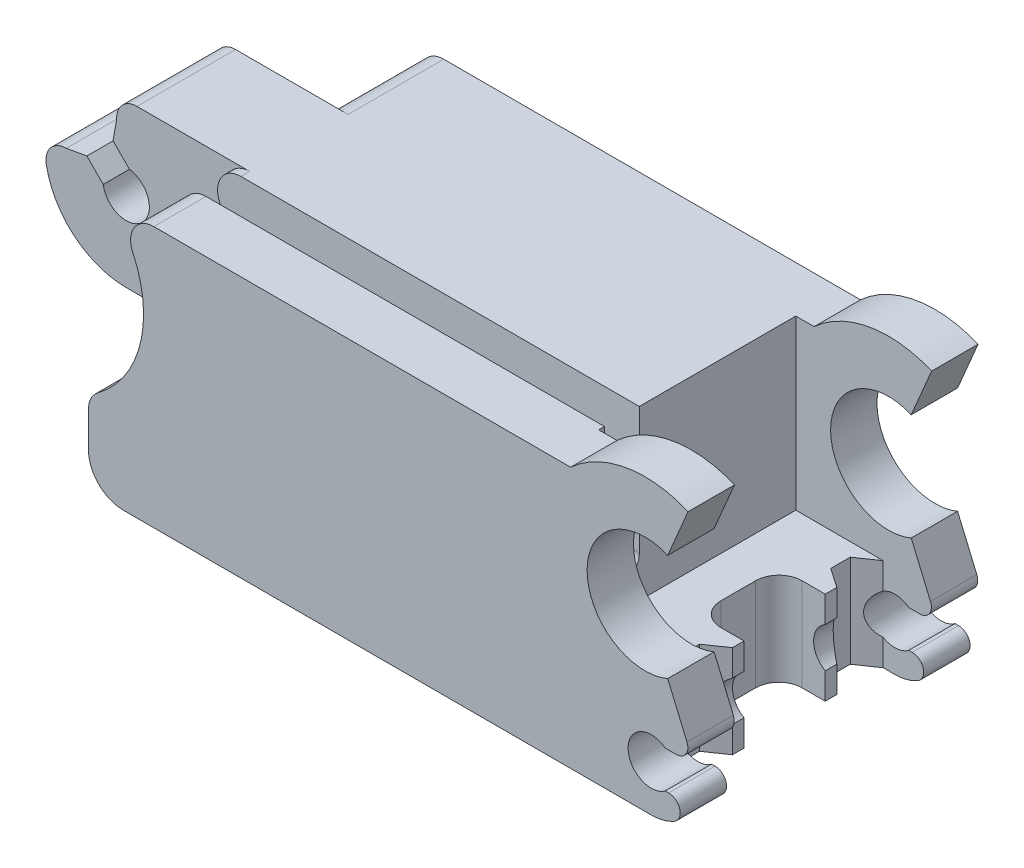
SolidWorks part; units mm, degrees
ref_plane "Front Plane" through (0, 0, 0) normal (0, 0, 1) x (1, 0, 0)
ref_plane "Top Plane" through (0, 0, 0) normal (0, 1, 0) x (1, 0, 0)
ref_plane "Right Plane" through (0, 0, 0) normal (1, 0, 0) x (0, 0, -1)
sketch "Sketch1" plane through (0, 0, 0) normal (0, 0, 1) x (1, 0, 0)
  line L0 (0, 0) -> (9.5, 0) construction
  line L1 (-62.5, 9.5) -> (9.5, 9.5)
  line L2 (-62.5, 9.5) -> (-62.5, -15.5)
  line L3 (-62.5, -15.5) -> (9.5, -15.5)
  line L4 (9.5, 9.5) -> (9.5, -15.5)
  line L5 (0, 0) -> (3.7119, 8.7448) construction
  line L6 (3.7119, 8.7448) -> (1.856, 4.3724)
  line L7 (3.7119, -8.7448) -> (1.856, -4.3724)
  line L8 (1.736, -9.9) -> (1.736, -13.1)
  line L9 (1.736, -9.9) -> (4.2021, -9.9)
  line L10 (1.736, -13.1) -> (4.2021, -13.1)
  line L11 (-52.7172, 1.9799) -> (-54.9799, -0.2828)
  line L12 (-62.5, -15.5) -> (-43, -15.5)
  line L13 (-62.5, -15.5) -> (-62.5, -6.5)
  line L16 (-52.7172, 1.9799) -> (-54.1314, 3.3941)
  line L17 (-58.1668, 0.8188) -> (-59.6208, 2.2728)
  line L18 (-53, 0) -> (-53.8485, 0.8485) construction
  line L19 (-56.3941, 1.1314) -> (-58.1668, 0.8188)
  line L20 (-53, 7) -> (-6.4226, 7)
  line L21 (-54.9799, -0.2828) -> (-56.3941, 1.1314)
  line L22 (-54.1314, 3.3941) -> (-53.8188, 5.1668)
  line L23 (-53.8188, 5.1668) -> (-55.2728, 6.6208)
  line L24 (-53, -7) -> (-43, -7)
  line L25 (-43, -7) -> (-43, -15.5)
  line L26 (4.2021, -9.9) -> (3.7119, -8.7448)
  line L27 (-43, -7) -> (-43, 0) construction
  line L28 (-48, -7) -> (-48, -15.5)
  line L29 (-53, 0) -> (-55, 0) construction
  circle A0 centre (0, 0) radius 2 construction
  circle A1 centre (-53, 0) radius 2
  circle A2 centre (0, 0) radius 5
  circle A3 centre (0, 0) radius 9.5
  circle A4 centre (0.536, -11.5) radius 2
  circle A5 centre (0.536, -11.5) radius 4
  circle A6 centre (-53, 0) radius 7
  circle A8 centre (-53, 0) radius 6 construction
  circle A9 centre (-53, 0) radius 6.5 construction
  point P39 (4.536, -11.5)
  dimension "D1" = 4
  dimension "D2" = 4
  dimension "D4" = 10
  dimension "D9" = 4
  dimension "D13" = 8
  dimension "D20" = 12
  dimension "D23" = 19
  dimension "D3" = 53
  dimension "D5" = 25
  dimension "D6" = 9.5
  dimension "D8" = 67
  dimension "D10" = 2
  dimension "D12" = 3.2
  dimension "D16" = 3.2
  dimension "D14" = 2
  dimension "D15" = 4.536
  dimension "D24" = 10
  dimension "D21" = 5
  dimension "D18" = 125
  dimension "D19" = 1.8
  dimension "D25" = 45
  dimension "D7" = 4.5
  dimension "D11" = 2
  dimension "D17" = 5
  dimension "D22" = 0.5
extrude "Boss-Extrude1" add sketch "Sketch1" along normal mid plane 25 contours A6 L23 L22 L16 A1 L21 L19 L17 | A6 L24 L25 L3 A5 A3 L20 | A5 A3 L7 A2 L6 | A3 A5 | L9 A5 A3 L10 A4 | A5 L26 A3 region at (1.8485, 9.0856, 0) region at (-26.1779, -4.322, 0) region at (-48.1903, 4.8097, 0) region at (0.3999, -8.5786, 0) region at (0.4428, -9.4998, 0) region at (3.7778, -9.0652, 0)
fillet "Fillet1" radius 1 2 edges at (4.2021, -13.1, 0) (4.2021, -9.9, 0)
sketch "Sketch3" plane through (0, 0, 0) normal (0, 0, 1) x (1, 0, 0)
  line L0 (-43, -15.5) -> (0.536, -15.5) construction
  line L1 (-8, 10.2107) -> (7.5521, 10.2107)
  line L2 (-8, 10.2107) -> (-8, -15.5)
  line L3 (-8, -15.5) -> (7.5521, -15.5)
  line L4 (7.5521, 10.2107) -> (7.5521, -15.5)
  dimension "D1" = 8
extrude "Cut-Extrude1" cut sketch "Sketch3" against normal offset from surface 4 and the other way offset from surface 4 contours L4 L1 L2 L3 region at (-0.2239, -2.6446, 0) up to face at (-27.411, -3.1826, -12.5) other way up to face at (-27.411, -3.1826, 12.5)
sketch "Sketch5" plane through (0, 0, 12.5) normal (0, 0, 1) x (1, 0, 0)
  line L0 (-53, 7) -> (-6.4226, 7) construction
  line L1 (-43, -7) -> (-73.6432, -7)
  line L2 (-43, -7) -> (-43, 7)
  line L3 (-43, 7) -> (-73.6432, 7)
  line L4 (-73.6432, -7) -> (-73.6432, 7)
extrude "Cut-Extrude2" cut sketch "Sketch5" against normal offset from surface (8.25 mm away) 4.25 up to face at (-0.7087, -5.8791, 8.5) offset beyond the face yes
sketch "Sketch6" plane through (0, 0, -12.5) normal (0, 0, -1) x (-1, 0, 0)
  line L8 (43, -7) -> (73.6432, -7)
  line L9 (73.6432, -7) -> (73.6432, 7)
  line L10 (73.6432, 7) -> (43, 7)
  line L11 (43, 7) -> (43, -7)
  line L12 (43, -7) -> (73.6432, -7)
  line L13 (73.6432, -7) -> (73.6432, 7)
  line L14 (73.6432, 7) -> (43, 7)
  line L15 (43, 7) -> (43, -7)
  line M10 (43, -7) -> (53, -7)
  arc M11 (53, -7) -> (59.6208, 2.2728) centre (53, 0) ccw
  line M12 (59.6208, 2.2728) -> (58.1668, 0.8188)
  line M13 (58.1668, 0.8188) -> (56.3941, 1.1314)
  line M14 (56.3941, 1.1314) -> (54.9799, -0.2828)
  arc M15 (54.9799, -0.2828) -> (52.7172, 1.9799) centre (53, 0) cw
  line M16 (52.7172, 1.9799) -> (54.1314, 3.3941)
  line M17 (54.1314, 3.3941) -> (53.8188, 5.1668)
  line M18 (53.8188, 5.1668) -> (55.2728, 6.6208)
  arc M19 (55.2728, 6.6208) -> (53, 7) centre (53, 0) ccw
  line M20 (53, 7) -> (6.4226, 7)
  dimension "D1" = 0
extrude "Cut-Extrude3" cut sketch "Sketch6" against normal offset from surface (8.25 mm away) 4.25 contours M10 M11 M12 M13 M14 M15 M16 M17 M18 M19 M20 region at (-49.9173, -0.455, -12.5) up to face at (-0.7087, -5.8791, -8.5) offset beyond the face yes
sketch "Sketch7" plane through (0, 0, 0) normal (0, 0, 1) x (1, 0, 0)
  line L9 (-55.2728, 6.6208) -> (-53.8188, 5.1668)
  line L10 (-55.2728, 6.6208) -> (-53.8188, 5.1668)
  line L11 (-53.8188, 5.1668) -> (-54.1314, 3.3941)
  line L12 (-53.8188, 5.1668) -> (-54.1314, 3.3941)
  line L13 (-54.1314, 3.3941) -> (-52.7172, 1.9799)
  line L14 (-54.1314, 3.3941) -> (-52.7172, 1.9799)
  line L15 (-43, 7) -> (-53, 7)
  line L16 (-43, -7) -> (-43, 7)
  line L17 (-54.9799, -0.2828) -> (-56.3941, 1.1314)
  line L25 (-43, -7) -> (-43, 7)
  line L27 (-54.9799, -0.2828) -> (-56.3941, 1.1314)
  line L28 (-56.3941, 1.1314) -> (-58.1668, 0.8188)
  line L29 (-56.3941, 1.1314) -> (-58.1668, 0.8188)
  line L30 (-58.1668, 0.8188) -> (-59.6208, 2.2728)
  line L31 (-58.1668, 0.8188) -> (-59.6208, 2.2728)
  line L32 (-43, 7) -> (-53, 7)
  line L34 (-53, -7) -> (-43, -7)
  line L37 (-53, -7) -> (-43, -7)
  arc A1 (-53, 7) -> (-55.2728, 6.6208) centre (-53, 0) ccw
  arc A5 (-53, 7) -> (-55.2728, 6.6208) centre (-53, 0) ccw
  arc A9 (-54.9799, -0.2828) -> (-52.7172, 1.9799) centre (-53, 0) ccw
  arc A10 (-54.9799, -0.2828) -> (-52.7172, 1.9799) centre (-53, 0) ccw
  arc A11 (-59.6208, 2.2728) -> (-53, -7) centre (-53, 0) ccw
  arc A12 (-59.6208, 2.2728) -> (-53, -7) centre (-53, 0) ccw
  dimension "D1" = 0
fillet "Fillet2" radius 1.75 2 edges at (-59.6208, 2.2728, 0) (-55.2728, 6.6208, 0)
sketch "Sketch8" [suppressed] plane through (0, 0, -4.25) normal (0, 0, 1) x (1, 0, 0)
  line L0 (-53, 7) -> (-43, 7)
  line L1 (-43, 7) -> (-43, -7)
  line L2 (-43, -7) -> (-53, -7)
  arc A0 (-54.9799, -0.2828) -> (-52.7172, 1.9799) centre (-53, 0) ccw construction
  arc A1 (-54.9799, -0.2828) -> (-52.7172, 1.9799) centre (-53, 0) ccw
  circle A2 centre (-53, 0) radius 6 construction
  circle A3 centre (-53, 0) radius 7
  dimension "D1" = 12
sketch "Sketch10" plane through (0, 0, 4.25) normal (0, 0, 1) x (1, 0, 0)
  line L1 (-48, -7) -> (-48, -15.5) construction
  line L2 (-48, -7) -> (-48, -15.5)
  line L3 (-43, 7) -> (-46.2131, 7)
  line L6 (-52.0708, 7) -> (-43, 7) construction
  line L7 (-43, 7) -> (-43, -15.5)
  line L8 (-43, -15.5) -> (-48, -15.5)
  arc A0 (3.7119, 8.7448) -> (-6.4226, 7) centre (0, 0) ccw construction
  arc A1 (-54.9799, -0.2828) -> (-52.7172, 1.9799) centre (-53, 0) ccw construction
  arc A2 (3.7119, 8.7448) -> (-6.4226, 7) centre (0, 0) ccw construction
  arc A3 (-54.9799, -0.2828) -> (-52.7172, 1.9799) centre (-53, 0) ccw construction
  circle A4 centre (-53, 0) radius 9.75
  line M9 (-53, -7) -> (-43, -7)
  line M10 (-43, -7) -> (-43, 7)
  line M11 (-43, 7) -> (-52.0708, 7)
  dimension "D1" = 9.5
  dimension "D2" = 19.5
extrude "Boss-Extrude3" add sketch "Sketch10" along normal up to surface (8.25 mm away) contours A4 M9 M10 M11 | A4 L2 L8 L7 M9 region at (-45.4396, -11.3712, 4.25) region at (-43.889, -3.8566, 4.25) up to face at (-6.0933, -5.8791, 12.5)
sketch "Sketch41" plane through (0, 0, -4.25) normal (0, 0, -1) x (-1, 0, 0)
  line L0 (43, 7) -> (46.2131, 7) construction
  line L1 (43, 7) -> (43, -15.5) construction
  line L2 (43, -15.5) -> (48, -15.5) construction
  line L3 (48, -7) -> (48, -15.5) construction
  line L4 (43, 7) -> (46.2131, 7)
  line L5 (43, 7) -> (43, -15.5)
  line L6 (43, -15.5) -> (48, -15.5)
  line L7 (48, -7) -> (48, -15.5)
  circle A1 centre (53, 0) radius 9.75
  circle A2 centre (53, 0) radius 9.75
  line M10 (52.0708, 7) -> (43, 7)
  line M11 (43, 7) -> (43, -7)
  line M12 (43, -7) -> (53, -7)
  dimension "D1" = 0
extrude "Boss-Extrude6" add sketch "Sketch41" along normal up to surface (8.25 mm away) contours A2 L5 L6 L7 M12 | A2 M10 M11 M12 region at (-44.6065, 6.8564, -4.25) region at (-45.4396, -11.3712, -4.25) up to face at (-6.0933, -5.8791, -12.5)
fillet "Fillet4" radius 2 4 edges at (-48, -8.3703, 8.375) (-46.2131, 7, 8.375) (-48, -8.3703, -8.375) (-46.2131, 7, -8.375)
ref_plane "Plane1" through (0, 0, 6.5) normal (0, 0, 1) x (1, 0, 0)
sketch "Sketch11" plane through (0, 0, 6.5) normal (0, 0, -1) x (-1, 0, 0)
  line L0 (51.8208, 5.4642) -> (1.1792, -5.4642)
  arc A0 (52.7172, 1.9799) -> (54.9799, -0.2828) centre (53, 0) ccw construction
  arc A1 (52.7172, 1.9799) -> (54.9799, -0.2828) centre (53, 0) ccw construction
  arc A2 (-1.9537, -4.6025) -> (-1.9537, 4.6025) centre (0, 0) ccw construction
  arc A3 (-1.9537, -4.6025) -> (-1.9537, 4.6025) centre (0, 0) ccw construction
  circle A4 centre (53, 0) radius 5 construction
  circle A5 centre (0, 0) radius 5 construction
  circle A6 centre (53, 0) radius 5.59 construction
  circle A7 centre (0, 0) radius 5.59 construction
  dimension "D3" = 0.59
sweep "Cut-Sweep1" cut path "Sketch11" circular profile diameter 3 parameters "D3"=3
fillet "Fillet6" radius 3 2 edges at (-48, -15.5, 8.375) (-48, -15.5, -8.375)
sketch "Sketch24" plane through (0, 0, 0) normal (0, 0, 1) x (1, 0, 0)
  line L0 (-45, -15.5) -> (0.536, -15.5) construction
  line L1 (-45, -15.5) -> (0.536, -15.5) construction
  line L6 (-24.5, -13.5) -> (-24.5, -15.5) construction
  line L7 (-11.5, -13.5) -> (-11.5, -15.5) construction
  line L8 (-41.5, -13.5) -> (-41.5, -15.5)
  line L9 (-28.5, -13.5) -> (-28.5, -15.5)
  line L10 (-41.5, -15.5) -> (-28.5, -15.5)
  line L11 (-24.5, -15.5) -> (-11.5, -15.5) construction
  line L12 (-35, -7) -> (-48, -7)
  line L13 (-48, -9.4373) -> (-48, -12.5) construction
  line L14 (-48, -7) -> (-48, -15.5)
  line L15 (-48, -15.5) -> (-28.5, -15.5)
  circle A0 centre (-18, -13.5) radius 2 construction
  arc A5 (-54.9799, -0.2828) -> (-52.7172, 1.9799) centre (-53, 0) ccw construction
  arc A6 (-54.9799, -0.2828) -> (-52.7172, 1.9799) centre (-53, 0) ccw construction
  circle A7 centre (-35, -13.5) radius 2 construction
  arc A8 (-11.5, -13.5) -> (-24.5, -13.5) centre (-18, -13.5) ccw construction
  arc A9 (-28.5, -13.5) -> (-41.5, -13.5) centre (-35, -13.5) ccw
  circle A10 centre (-18, -13.5) radius 2.2 construction
  circle A11 centre (-35, -13.5) radius 2.2
  dimension "D1" = 4
  dimension "D2" = 18
  dimension "D3" = 4.5
  dimension "D4" = 18
  dimension "D5" = 0.2
extrude "Cut-Extrude6" cut sketch "Sketch24" against normal mid plane 8.5 contours A10 L11 L7 A8 L6 | A11 L10 L9 A9 L8 | A9 L12 L14 L15 L8 region at (-39.4864, -9.0136, 0) region at (-44.0872, -10.8555, 0)
sketch "Sketch45" plane through (0, 0, 0) normal (0, 0, 1) x (1, 0, 0)
  line L0 (3.612, -8.5093) -> (1.9537, -4.6025) construction
  line L1 (3.612, -8.5093) -> (1.9537, -4.6025)
  arc A0 (1.736, -9.9) -> (1.736, -13.1) centre (0.536, -11.5) ccw construction
  arc A1 (1.736, -9.9) -> (1.736, -13.1) centre (0.536, -11.5) ccw
sketch "Sketch47" plane through (0, 7, 0) normal (0, 1, 0) x (1, 0, 0)
  line L0 (-8, -5) -> (-44.0122, -5) construction
  line L1 (-5.5113, -5) -> (-48.8713, -5)
  line L2 (-44.0122, -8) -> (-8, -8) construction
  line L3 (-48.8713, -8) -> (-5.5113, -8)
  line L4 (-48.8713, -8) -> (-48.8713, -5)
  line L5 (-5.5113, -5) -> (-5.5113, -8)
extrude "Cut-Extrude7" cut sketch "Sketch47" against normal up to surface (11.5293 mm away) up to face at (-43.9108, 3.7419, 6.6784)
sketch "Sketch50" plane through (0, 0, 8.5) normal (0, 0, -1) x (-1, 0, 0)
  line L0 (0.464, -13.2321) -> (0.464, -15.5)
  line L1 (8, -15.5) -> (-0.536, -15.5) construction
  line L2 (8, 7) -> (8, -15.5) construction
  line L3 (8, 7) -> (8, -15.5)
  line L4 (0.464, -15.5) -> (8, -15.5)
  line L5 (0.464, -9.7679) -> (0.464, -7.5)
  line L6 (0.464, -7.5) -> (8, -7.5)
  arc A0 (-1.736, -13.1) -> (-1.736, -9.9) centre (-0.536, -11.5) ccw construction
  arc A1 (-1.736, -13.1) -> (-1.736, -9.9) centre (-0.536, -11.5) ccw
  arc M11 (-1.736, -9.9) -> (-1.736, -13.1) centre (-0.536, -11.5) cw
  line M15 (-0.536, -15.5) -> (8, -15.5)
  line M16 (8, -15.5) -> (8, 7)
  dimension "D1" = 4
  dimension "D2" = 4
extrude "Boss-Extrude7" add sketch "Sketch50" along normal up to vertex contours L6 L5 L0 M11 M15 M16 region at (-4.3746, -11.5, 8.5) up to point (0.536, -15.5, -8.5)
sketch "Sketch51" plane through (0, -15.5, 0) normal (0, -1, 0) x (1, 0, 0)
  line L0 (-0.464, -8.5) -> (-0.464, 8.5) construction
  line L1 (-0.464, -8.5) -> (-0.464, 8.5)
  line L2 (-2.144, 5.66) -> (-2.144, 7.34)
  line L3 (-2.144, 7.34) -> (-0.464, 8.5)
  line L4 (-2.144, 6.5) -> (-0.464, 6.5) construction
  line L5 (-2.144, 5.66) -> (-0.464, 4.5)
  line L6 (-0.464, 0) -> (-3.9441, 0) construction
  line L7 (-2.144, -5.66) -> (-0.464, -4.5)
  line L8 (-2.144, -5.66) -> (-2.144, -7.34)
  line L9 (-2.144, -7.34) -> (-0.464, -8.5)
  line L12 (-0.464, 3.5) -> (-0.464, -4)
  line L13 (-0.464, 3.5) -> (-4.464, 3.5)
  line L14 (-0.464, 3.5) -> (-0.464, -3.5)
  line L15 (-0.464, -3.5) -> (-4.464, -3.5)
  line L16 (-4.464, 3.5) -> (-4.464, -3.5)
  point P2 (-2.144, 6.5)
  point P6 (-2.144, 6.5)
  point P17 (-4.464, 0)
  point P20 (0, 0)
  point P21 (0, 0)
  point P23 (-4.464, -3.4312)
  point P24 (0, 0)
  point P25 (0, 0)
  point P26 (-8, -3.3962)
  point P27 (0, 0)
  line M26 (-0.464, -8.5) -> (-0.464, 8.5)
  dimension "D1" = 2
  dimension "D2" = 1.68
  dimension "D3" = 1.68
  dimension "D4" = 7
  dimension "D5" = 4
extrude "Cut-Extrude8" cut sketch "Sketch51" against normal up to surface (8 mm away) contours L2 L5 L1 L3 | L8 L9 L7 M26 | L13 L16 L15 L12 region at (-1.1896, -15.5, -6.5) region at (-1.1896, -15.5, 6.5) region at (-2.464, -15.5, 0) up to face at (-4.232, -7.5, 0)
fillet "Fillet10" radius 2 2 edges at (-4.464, -11.5, 3.5) (-4.464, -11.5, -3.5)
equation "\"mainSnapAngle\"= 67deg"
equation "\"D8@Sketch1\"=\"mainSnapAngle\""
equation "\"jointDistance\"= 53mm"
equation "\"mountBearingOD\"= 10mm"
equation "\"D3@Sketch1\"=\"jointDistance\""
equation "\"D4@Sketch1\"=\"mountBearingOD\""
equation "\"shaftDiameter\"= 4mm"
equation "\"D12@Sketch1\"=\"shaftDiameter\"*0.8"
equation "\"D2@Sketch1\"=\"shaftDiameter\""
equation "\"D1@Sketch1\"=\"shaftDiameter\""
equation "\"D16@Sketch1\"=\"D2@Sketch1\"*0.8"
equation "\"UgrooveOD\"= 12mm"
equation "\"D20@Sketch1\"=\"UgrooveOD\""
equation "\"D1@Sketch8\"=\"UgrooveOD\""
equation "\"D24@Sketch1\"= \"D23@Sketch1\" / 2 + 0.5"
equation "\"D2@Sketch10\"=\"D1@Sketch10\"*2+0.5"
equation "\"grooveDiameter\"= 10mm"
equation "\"tendonDiameter\"= 1.18mm"
equation "\"D3@Sketch11\"=\"tendonDiameter\"/2"
equation "\"D1@Sketch11\"=\"grooveDiameter\""
equation "\"D1@Sketch3\"=\"UgrooveOD\"/2+2"
equation "\"D2@Sketch50\"=\"D1@Sketch50\""
equation "\"D2@Sketch51\"=\"tendonDiameter\" +0.5"
equation "\"D3@Sketch51\"=\"D2@Sketch51\""
